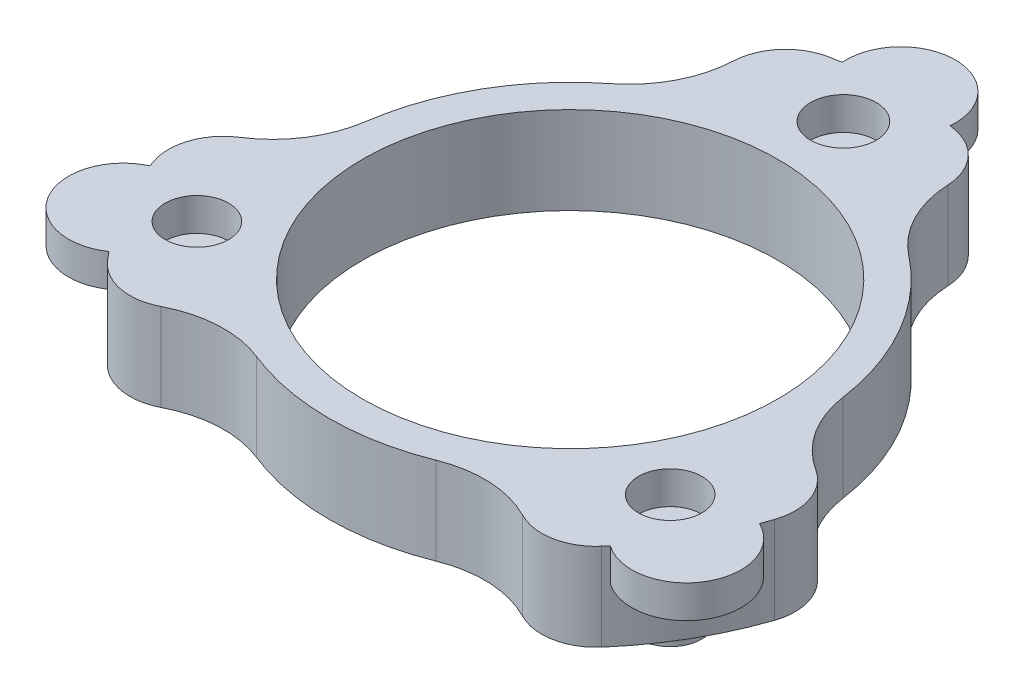
SolidWorks part; units mm, degrees
ref_plane "Спереди" through (0, 0, 0) normal (0, 0, 1) x (1, 0, 0)
ref_plane "Сверху" through (0, 0, 0) normal (0, 1, 0) x (1, 0, 0)
ref_plane "Справа" through (0, 0, 0) normal (1, 0, 0) x (0, 0, -1)
sketch "Sketch1" plane through (0, 0, 0) normal (0, 1, 0) x (1, 0, 0)
  circle A0 centre (0, 0) radius 19
  dimension "D1" = 38
extrude "Boss-Extrude1" add sketch "Sketch1" along normal blind 3.5
sketch "Sketch2" plane through (0, 0, 0) normal (0, 1, 0) x (1, 0, 0)
  circle A0 centre (0, 0) radius 30
  circle A1 centre (0, 0) radius 19
  circle A2 centre (0, 0) radius 25 construction
  circle A3 centre (0, 25) radius 2.8
  circle A4 centre (21.6506, -12.5) radius 2.8
  circle A5 centre (-21.6506, -12.5) radius 2.8
  point P16 (0, 0)
  dimension "D2" = 50
  dimension "D1" = 3
extrude "Boss-Extrude2" add sketch "Sketch2" along normal blind 8
sketch "Sketch4" plane through (0, 0, 0) normal (0, -1, 0) x (1, 0, 0)
  circle A0 centre (-21.6506, 12.5) radius 2.9
  circle A1 centre (21.6506, 12.5) radius 2.9
  circle A2 centre (0, -25) radius 2.9
  point P9 (0, 0)
  dimension "D1" = 3
extrude "Boss-Extrude3" add sketch "Sketch4" along normal blind 2 and the other way blind 8
sketch "Sketch5" plane through (0, 8, 0) normal (0, 1, 0) x (1, 0, 0)
  circle A0 centre (-26.1031, -14.7861) radius 5
  circle A1 centre (0, 0) radius 30 construction
  circle A2 centre (0.2465, 29.999) radius 5
  circle A3 centre (25.8567, -15.2129) radius 5
  point P10 (0, 0)
  dimension "D1" = 3
extrude "Boss-Extrude4" add sketch "Sketch5" against normal blind 3
sketch "Sketch3" plane through (0, 3.5, 0) normal (0, 1, 0) x (1, 0, 0)
  circle A0 centre (0, 0) radius 19
extrude "Cut-Extrude1" cut sketch "Sketch3" against normal blind 10
sketch "Sketch6" plane through (0, 8, 0) normal (0, 1, 0) x (1, 0, 0)
  circle A0 centre (0, 25) radius 3
  circle A1 centre (21.6506, -12.5) radius 2.9
  circle A2 centre (-21.6506, -12.5) radius 2.9
extrude "Cut-Extrude2" cut sketch "Sketch6" against normal blind 3
sketch "Sketch7" plane through (0, 8, 0) normal (0, 1, 0) x (1, 0, 0)
  line L0 (0, 0) -> (-13.774, 37.8437)
  line L1 (0, 0) -> (-43.9393, -7.7477)
  line L2 (-13.774, 37.8437) -> (-43.9393, -7.7477)
  line L3 (39.6606, -6.9932) -> (15.26, 41.9264)
  line L4 (0, 0) -> (15.26, 41.9264)
  line L5 (0, 0) -> (39.6606, -6.9932)
  line L6 (-25.8866, -30.8505) -> (28.6794, -34.1787)
  line L7 (0, 0) -> (28.6794, -34.1787)
  line L8 (0, 0) -> (-25.8866, -30.8505)
  circle A0 centre (0, 0) radius 22.0646
  point P12 (0, 0)
  arc M11 (-23.2848, -18.9161) -> (22.9709, -19.2961) centre (0, 0) ccw
  arc M13 (28.0242, -10.7072) -> (5.2255, 29.5414) centre (0, 0) ccw
  arc M15 (-4.7394, 29.6233) -> (-28.1963, -10.2453) centre (0, 0) ccw
  dimension "D1" = 3
extrude "Cut-Extrude3" cut sketch "Sketch7" against normal blind 13 contours L0 L2 L1 M15 | A0 L0 L1 M15 | L5 L3 L4 M13 | A0 L5 L4 M13 | L8 L6 L7 M11 | A0 L8 L7 M11 region at (-20.9182, 8, -12.0771) region at (20.9182, 8, -12.0771) region at (0, 8, 24.1542) region at (-26.4716, 8, -15.2834) region at (13.2966, 8, -34.8634) region at (23.5548, 8, 28.9381)
fillet "Fillet1" radius 10 6 edges at (-21.7294, 4, 3.8315) (-14.1829, 4, 16.9025) (14.1829, 4, 16.9025) (21.7294, 4, 3.8315) (7.5465, 4, -20.734) (-7.5465, 4, -20.734)
fillet "Fillet2" radius 5 6 edges at (-10.2606, 4, -28.1908) (-29.5442, 4, 5.2094) (-19.2836, 4, 22.9813) (19.2836, 4, 22.9813) (29.5442, 4, 5.2094) (10.2606, 4, -28.1908)
sketch "Sketch8" plane through (0, 8, 0) normal (0, 1, 0) x (1, 0, 0)
  circle A0 centre (-16.5249, 9.377) radius 4
  circle A1 centre (0, 0) radius 19
